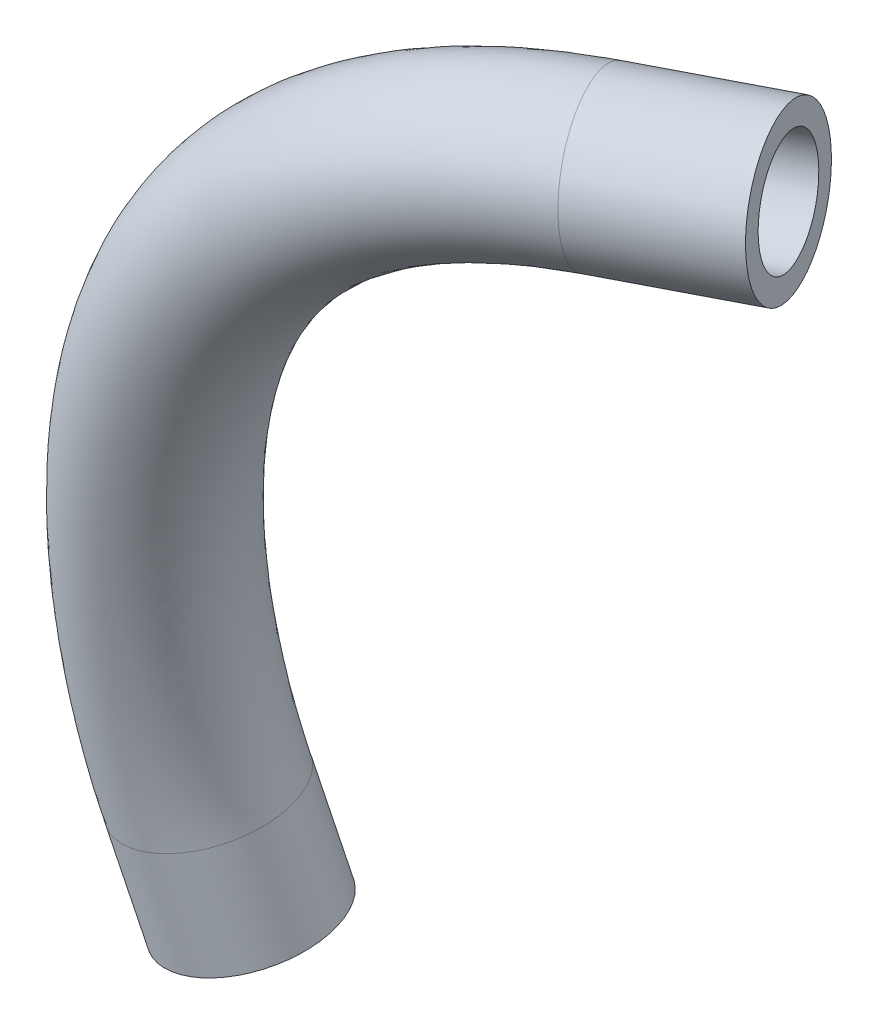
SolidWorks part; units mm, degrees
note: The reader was unsure of these and kept them because the rebuilt part matched: shared geometry of "3DSketch1<2>".
material "Silicon Rubber"
ref_plane "X-Y Datum" through (0, 0, 0) normal (0, 0, 1) x (1, 0, 0)
ref_plane "X-Z Datum" through (0, 0, 0) normal (0, 1, 0) x (1, 0, 0)
ref_plane "Y-Z Datum" through (0, 0, 0) normal (1, 0, 0) x (0, 0, -1)
sketch3d "3DSketch1"
  line L0 (1.5071, -46.7359, -12.1218) -> (-2.8988, -28.462, -9.0304)
  line L1 (67.314, 102.1503, -7.8317) -> (90.8083, 103.905, -17.3236)
  line L2 (67.314, 102.1503, -7.8317) -> (90.8083, 103.905, -17.3236) construction
  line L3 (67.314, 102.1503, -7.8317) -> (69.1142, 102.2848, -8.559) construction
  line L4 (90.8083, 103.905, -17.3236) -> (73.6963, 102.627, -10.4102) construction
  line L5 (-2.8988, -28.462, -9.0304) -> (-1.1675, -35.643, -10.2452) construction
  circle A10 centre (90.8083, 103.905, -17.3236) radius 9.5 construction
  circle A11 centre (73.6963, 102.627, -10.4102) radius 8.23 construction
  circle A12 centre (90.8083, 103.905, -17.3236) radius 9.5 construction
  circle A13 centre (73.6963, 102.627, -10.4102) radius 8.23 construction
  circle A14 centre (-2.8988, -28.462, -9.0304) radius 9.525 construction
  circle A15 centre (-1.1675, -35.643, -10.2452) radius 9.9344 construction
  circle A16 centre (-2.8988, -28.462, -9.0304) radius 9.525 construction
  circle A17 centre (-1.1675, -35.643, -10.2452) radius 9.9344 construction
  spline S0 degree 3 poles (-2.8988, -28.462, -9.0304) (-12.7334, 12.3277, -2.13) (3.6944, 97.3989, 17.8712) (67.314, 102.1503, -7.8317) knots 0 0 0 0 1 1 1 1
  point P5 (82.0211, 103.2487, -13.7735)
  point P9 (66.0837, 102.0584, -7.3346)
  point P11 (82.0211, 103.2487, -13.7735)
  point P13 (66.0837, 102.0584, -7.3346)
  point P15 (-5.1018, -19.3251, -7.4847)
  point P19 (-3.4651, -26.1134, -8.6331)
  point P21 (-5.1018, -19.3251, -7.4847)
  point P24 (-3.4651, -26.1134, -8.6331)
  dimension "D2" = 19.05
  dimension "D1" = 25.4
sweep "Sweep1" add path "3DSketch1" parameters "D3"=26.9875
sweep "Cut-Sweep1" cut path "3DSketch1<2>" circular profile diameter 19.05 parameters "D3"=19.05
sketch3d "3DSketch1<2>" same geometry as "3DSketch1"
